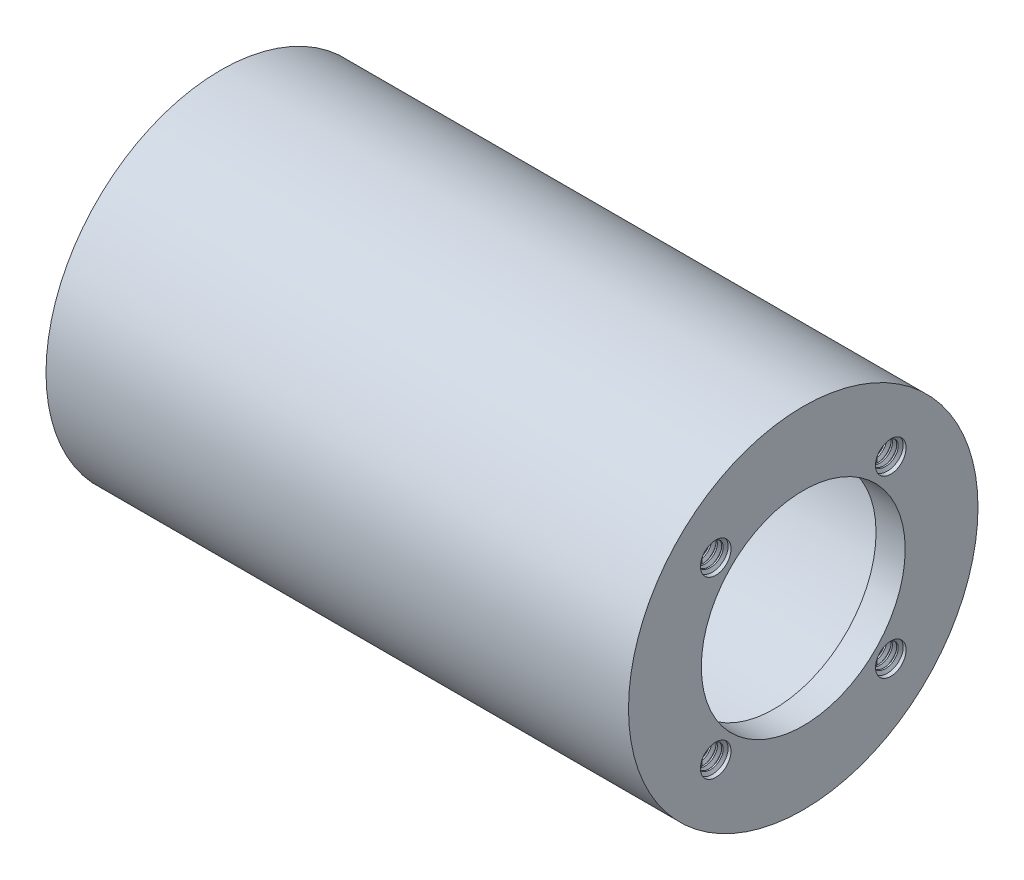
SolidWorks part; units mm, degrees
material "Copper"
ref_plane "Front Plane" through (0, 0, 0) normal (0, 0, 1) x (1, 0, 0)
ref_plane "Top Plane" through (0, 0, 0) normal (0, 1, 0) x (1, 0, 0)
ref_plane "Right Plane" through (0, 0, 0) normal (1, 0, 0) x (0, 0, -1)
sketch "Sketch3" plane through (0, 0, 0) normal (1, 0, 0) x (0, 0, -1)
  circle A0 centre (0, 0) radius 12
  circle A1 centre (0, 0) radius 7
  dimension "D1" = 24
  dimension "D2" = 14
extrude "Boss-Extrude1" add sketch "Sketch3" along normal blind 40
sketch "Sketch4" plane through (0, 0, 0) normal (1, 0, 0) x (0, 0, -1)
  circle A0 centre (0, 0) radius 11
  dimension "D1" = 22
extrude "Cut-Extrude1" cut sketch "Sketch4" along normal blind 38
sketch "Sketch5" plane through (0, 0, 0) normal (1, 0, 0) x (0, 0, -1)
  line L0 (0, 0) -> (0, 12) construction
  line L1 (0, 0) -> (12, 0) construction
  line L2 (0, 0) -> (8.4853, 8.4853) construction
  circle A0 centre (0, 0) radius 12 construction
  circle A1 centre (0, 0) radius 8.5 construction
  circle A2 centre (6.0104, 6.0104) radius 1.05
  circle A3 centre (6.0104, -6.0104) radius 1.05
  circle A4 centre (-6.0104, -6.0104) radius 1.05
  circle A5 centre (-6.0104, 6.0104) radius 1.05
  point P20 (0, 0)
  dimension "D2" = 17
  dimension "D3" = 2.1
  dimension "D1" = 45
  dimension "D4" = 4
extrude "Cut-Extrude2" cut sketch "Sketch5" against normal through all from surface at 40 starting at face at (40, 0, -12)
thread "Thread1" pitch 0.4 start angle 0, offset 0, length 0, pitch 0.4, diameter 2.1
ref_plane "Plane1" through (40, 6.0104, 7.0604) normal (0, -1, 0) x (0, 0, 1)
sketch "Thread Profile1" plane through (40, 6.0104, 7.0604) normal (0, -1, 0) x (0, 0, 1)
  line L0 (0, 0) -> (0, 0.4) construction
  line L11 (0, 0) -> (0, 0.35)
  line L12 (0, 0.35) -> (-0.2165, 0.225)
  line L13 (-0.2165, 0.225) -> (-0.2165, 0.125)
  line L15 (-0.2165, 0.125) -> (0, 0)
  line L17 (-0.2165, 0.175) -> (0, 0.175) construction
  point P2 (0, 0)
  dimension "Pitch" = 0.4
  dimension "Profile_Angle" = 60
  dimension "Profile_Land" = 0.1
  dimension "Profile_Height" = 0.2165
thread "Thread2" pitch 0.4 profile "Thread Profile2" start angle 0, offset 0, length 0, pitch 0.4, diameter 2.1
ref_plane "Plane2" through (40, 6.0104, -4.9604) normal (0, -1, 0) x (0, 0, 1)
sketch "Thread Profile2" plane through (40, 6.0104, -4.9604) normal (0, -1, 0) x (0, 0, 1)
  line L0 (0, 0) -> (0, 0.4) construction
  line L11 (0, 0) -> (0, 0.35)
  line L12 (0, 0.35) -> (-0.2165, 0.225)
  line L13 (-0.2165, 0.225) -> (-0.2165, 0.125)
  line L15 (-0.2165, 0.125) -> (0, 0)
  line L17 (-0.2165, 0.175) -> (0, 0.175) construction
  point P2 (0, 0)
  dimension "Pitch" = 0.4
  dimension "Profile_Angle" = 60
  dimension "Profile_Land" = 0.1
  dimension "Profile_Height" = 0.2165
thread "Thread3" pitch 0.4 profile "Thread Profile3" start angle 0, offset 0, length 0, pitch 0.4, diameter 2.1
ref_plane "Plane3" through (40, -6.0104, 7.0604) normal (0, -1, 0) x (0, 0, 1)
sketch "Thread Profile3" plane through (40, -6.0104, 7.0604) normal (0, -1, 0) x (0, 0, 1)
  line L0 (0, 0) -> (0, 0.4) construction
  line L11 (0, 0) -> (0, 0.35)
  line L12 (0, 0.35) -> (-0.2165, 0.225)
  line L13 (-0.2165, 0.225) -> (-0.2165, 0.125)
  line L15 (-0.2165, 0.125) -> (0, 0)
  line L17 (-0.2165, 0.175) -> (0, 0.175) construction
  point P2 (0, 0)
  dimension "Pitch" = 0.4
  dimension "Profile_Angle" = 60
  dimension "Profile_Land" = 0.1
  dimension "Profile_Height" = 0.2165
thread "Thread4" pitch 0.4 profile "Thread Profile4" start angle 0, offset 0, length 0, pitch 0.4, diameter 2.1
ref_plane "Plane4" through (40, -6.0104, -4.9604) normal (0, -1, 0) x (0, 0, 1)
sketch "Thread Profile4" plane through (40, -6.0104, -4.9604) normal (0, -1, 0) x (0, 0, 1)
  line L0 (0, 0) -> (0, 0.4) construction
  line L11 (0, 0) -> (0, 0.35)
  line L12 (0, 0.35) -> (-0.2165, 0.225)
  line L13 (-0.2165, 0.225) -> (-0.2165, 0.125)
  line L15 (-0.2165, 0.125) -> (0, 0)
  line L17 (-0.2165, 0.175) -> (0, 0.175) construction
  point P2 (0, 0)
  dimension "Pitch" = 0.4
  dimension "Profile_Angle" = 60
  dimension "Profile_Land" = 0.1
  dimension "Profile_Height" = 0.2165
